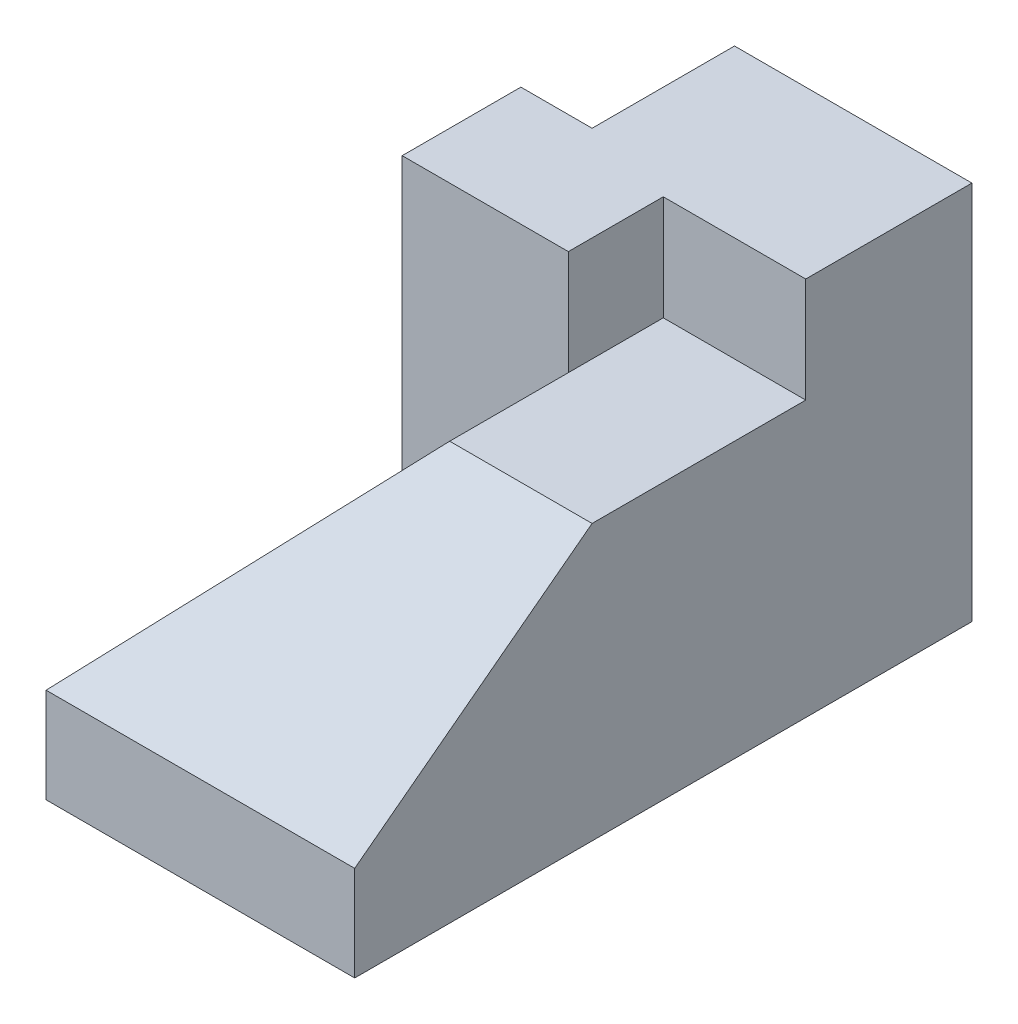
SolidWorks part; units mm, degrees
ref_plane "Front Plane" through (0, 0, 0) normal (0, 0, 1) x (1, 0, 0)
ref_plane "Top Plane" through (0, 0, 0) normal (0, 1, 0) x (1, 0, 0)
ref_plane "Right Plane" through (0, 0, 0) normal (1, 0, 0) x (0, 0, -1)
sketch "Sketch1" plane through (0, 0, 0) normal (0, 1, 0) x (1, 0, 0)
  line L0 (15, 100) -> (15, 130)
  line L1 (0, 0) -> (65, 0)
  line L2 (0, 0) -> (0, 100)
  line L3 (0, 100) -> (15, 100)
  line L4 (65, 0) -> (65, 100)
  line L5 (15, 130) -> (65, 130)
  line L6 (65, 130) -> (65, 100)
  line L7 (0, 75) -> (35, 75)
  line L8 (35, 75) -> (35, 95)
  line L9 (35, 100) -> (65, 100)
  line L10 (35, 95) -> (65, 95)
  point P11 (7.5, 100)
  dimension "D1" = 65
  dimension "D2" = 100
  dimension "D3" = 50
  dimension "D4" = 30
  dimension "D5" = 25
  dimension "D6" = 35
  dimension "D7" = 20
extrude "Boss-Extrude1" add sketch "Sketch1" along normal blind 20 contours L10 L8 L7 L2 L1 L4 region at (34.4178, 0, -42.7055)
extrude "Boss-Extrude2" add sketch "Sketch1<3>" along normal blind 80 contours L8 L10 L4 L6 L5 L0 L3 L2 L7 region at (32.797, 0, -104.4307)
sketch "Sketch1<3>" plane through (0, 0, 0) normal (0, 1, 0) x (1, 0, 0) same geometry as "Sketch1"
sketch "Sketch8" plane through (65, 0, 0) normal (1, 0, 0) x (0, 0, -1)
  line L0 (95, 57.9136) -> (50, 57.9136)
  line L1 (95, 80) -> (95, 20) construction
  line L2 (50, 57.9136) -> (0, 20)
  line L3 (95, 57.9136) -> (95, 20)
  line L4 (95, 20) -> (0, 20)
  dimension "D1" = 45
extrude "Boss-Extrude6" add sketch "Sketch8" against normal blind 30
sketch "Sketch9" plane through (0, 0, -75) normal (0, 0, 1) x (1, 0, 0)
  line L0 (0, 20) -> (35, 57.9136)
  line L1 (35, 57.9136) -> (35, 20)
  line L2 (35, 20) -> (0, 20)
extrude "Boss-Extrude7" add sketch "Sketch9" along normal blind 75
sketch "Sketch10" plane through (35, 0, 0) normal (1, 0, 0) x (0, 0, -1)
  line L0 (0, 57.9136) -> (50, 57.9136)
  line L1 (50, 57.9136) -> (0, 20)
  line L2 (0, 20) -> (0, 57.9136)
extrude "Cut-Extrude1" cut sketch "Sketch10" against normal up to next
